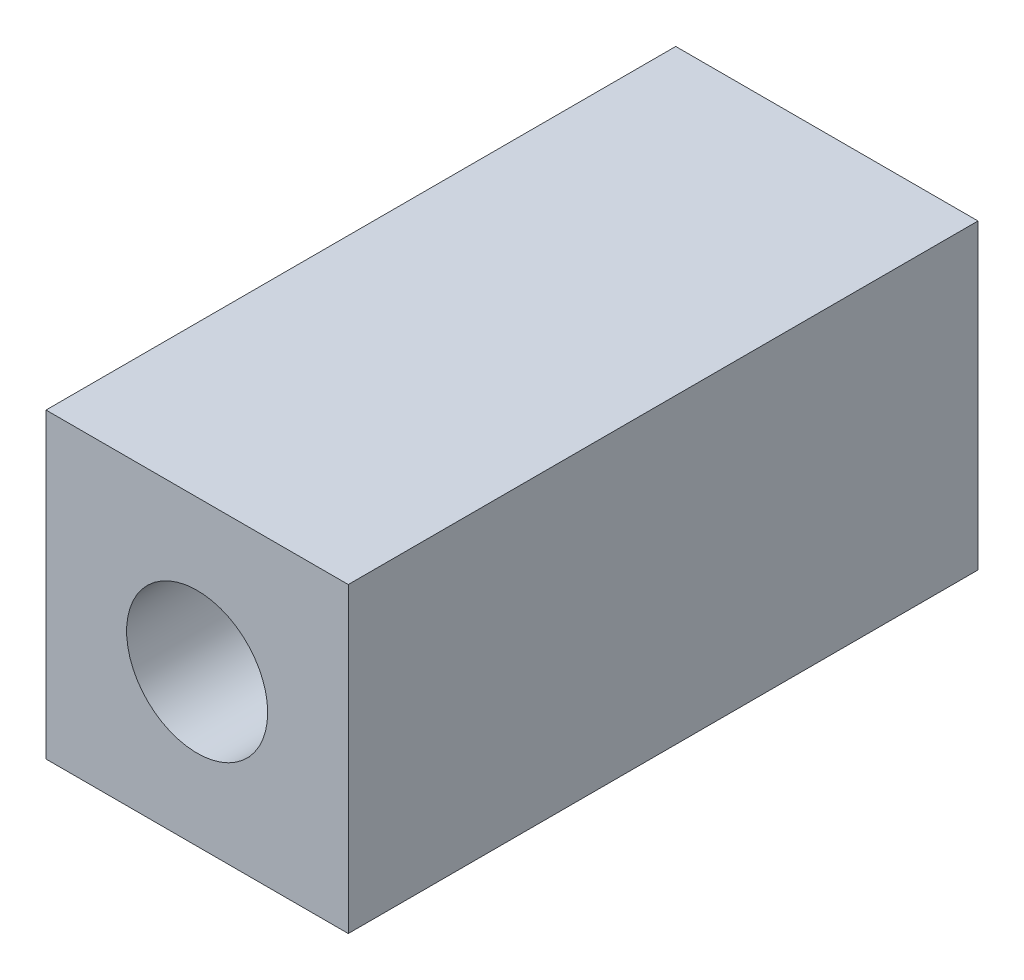
SolidWorks part; units mm, degrees
ref_plane "Front Plane" through (0, 0, 0) normal (0, 0, 1) x (1, 0, 0)
ref_plane "Top Plane" through (0, 0, 0) normal (0, 1, 0) x (1, 0, 0)
ref_plane "Right Plane" through (0, 0, 0) normal (1, 0, 0) x (0, 0, -1)
sketch "Sketch1" plane through (0, 0, 0) normal (0, 0, 1) x (1, 0, 0)
  line L1 (3, 3) -> (-3, 3)
  line L2 (3, 3) -> (3, -3)
  line L3 (3, -3) -> (-3, -3)
  line L4 (-3, 3) -> (-3, -3)
  line L5 (3, 3) -> (-3, -3) construction
  line L6 (3, -3) -> (-3, 3) construction
  circle A0 centre (0, 0) radius 1.4
  point P0 (0, 0)
  dimension "D1" = 2.8
  dimension "D2" = 6
  dimension "D3" = 6
extrude "Boss-Extrude1" add sketch "Sketch1" along normal blind 12.5
